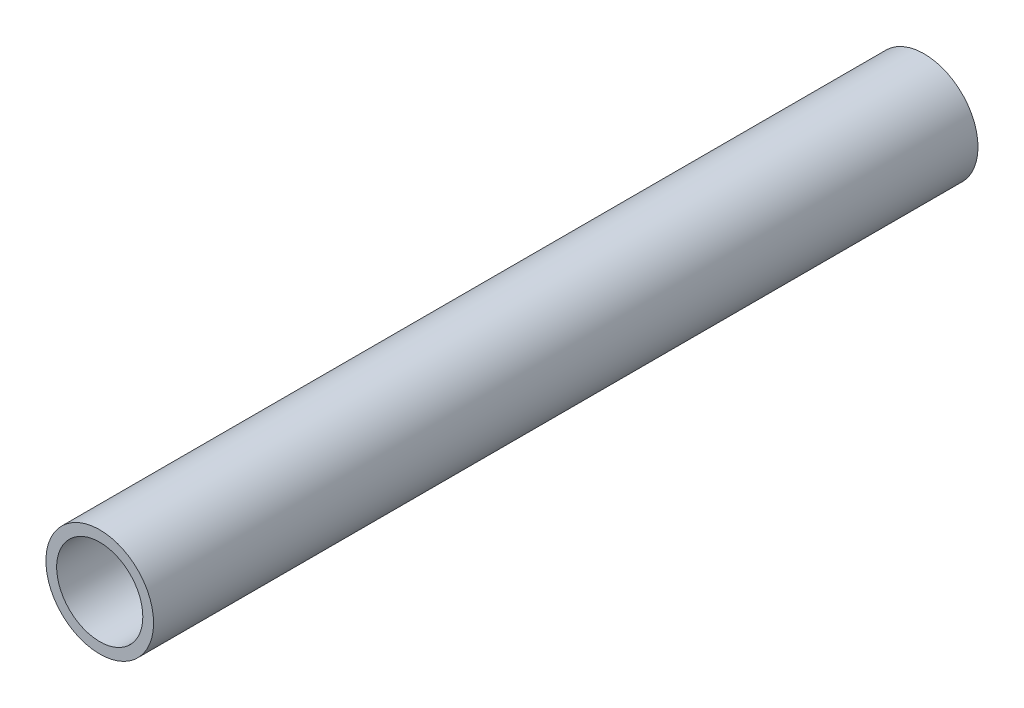
SolidWorks part; units mm, degrees
ref_plane "Front Plane" through (0, 0, 0) normal (0, 0, 1) x (1, 0, 0)
ref_plane "Top Plane" through (0, 0, 0) normal (0, 1, 0) x (1, 0, 0)
ref_plane "Right Plane" through (0, 0, 0) normal (1, 0, 0) x (0, 0, -1)
sketch "Sketch1" plane through (0, 0, 0) normal (0, 0, 1) x (1, 0, 0)
  circle A0 centre (0, 0) radius 1.25
  circle A1 centre (0, 0) radius 1
extrude "Boss-Extrude1" add sketch "Sketch1" along normal blind 19.14
